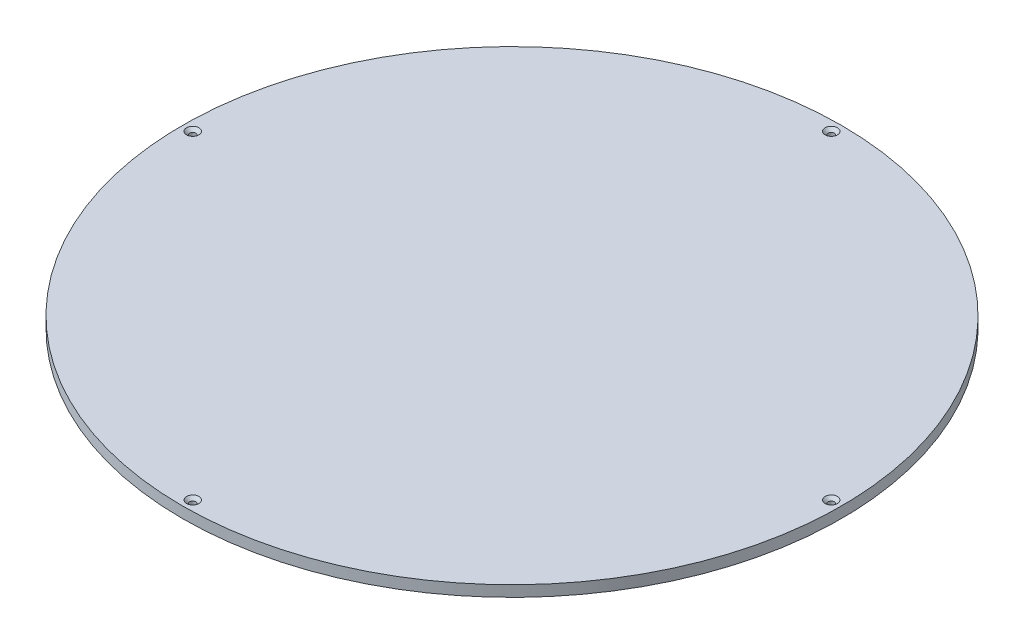
SolidWorks part; units mm, degrees
material "Pine"
ref_plane "Front Plane" through (0, 0, 0) normal (0, 0, 1) x (1, 0, 0)
ref_plane "Top Plane" through (0, 0, 0) normal (0, 1, 0) x (1, 0, 0)
ref_plane "Right Plane" through (0, 0, 0) normal (1, 0, 0) x (0, 0, -1)
sketch "Sketch1" plane through (0, 0, 0) normal (0, 1, 0) x (1, 0, 0)
  line L0 (-8.7941, 0) -> (197.1788, 0) construction
  circle A0 centre (0, 0) radius 160
  circle A1 centre (155, 0) radius 1.5
  circle A2 centre (0, -155) radius 1.5
  circle A3 centre (-155, 0) radius 1.5
  circle A4 centre (0, 155) radius 1.5
  point P16 (0, 0)
  dimension "D1" = 320
  dimension "D2" = 3
  dimension "D3" = 155
  dimension "D4" = 4
extrude "Boss-Extrude1" add sketch "Sketch1" against normal blind 5.333
chamfer "Chamfer1" distance 1.5 angle 45 4 edges at (155, 0, 1.5) (-155, 0, 1.5) (0, 0, -153.5) (0, 0, 156.5)
equation "\"rod_diameter\"= 8"
equation "\"rod_hole_thickness\"= 4"
equation "\"rod_radius\"= \"rod_diameter\" / 2"
equation "\"platter_diameter\"= 320"
equation "\"platter_radius\"= \"platter_diameter\" / 2"
equation "\"extruder_mount_hole_spacing\"= 75"
equation "\"arm_rod_spacing\"= 40"
equation "\"motor_level_rod_spacing\"= 15"
equation "\"linear_bearing_diameter\"= 15"
equation "\"z_rod_spacing\"= 75"
equation "\"platter_rod_spacing\"= 50"
equation "\"rod_nut_thickness\"= 6.5"
equation "\"rod_nut_inscribed_diameter\"= 13"
equation "\"z_height\"= 400"
equation "\"D1@Sketch1\"=\"platter_diameter\""
equation "\"D3@Sketch1\"=\"platter_radius\"-5"
equation "\"top_frame_spacing\"= 100"
equation "\"z_drive_rod_offset\"= 12"
equation "\"gear_pitch\"=2"
equation "\"r_gear_teeth\"= 450"
equation "\"theta_gear_teeth\"= 385"
equation "\"sheet_thickness\"=5.333"
equation "\"sheet_tab_hole_thickness\"= \"sheet_thickness\""
equation "\"sheet_tab_width\"= \"sheet_thickness\"*2"
equation "\"sheet_double_tab_width\"= 35"
equation "\"sheet_bolt_diameter\"= 3"
equation "\"sheet_bolt_length\"= 16"
equation "\"sheet_nut_diameter\"= 5.5"
equation "\"sheet_nut_thickness\"= 2.5"
equation "\"sheet_nut_depth\"= 10"
equation "\"bearing_outside_diameter\"= 22"
equation "\"bearing_thickness\"= 7"
equation "\"corner_part_thickness\"= \"sheet_thickness\" + \"bearing_thickness\""
equation "\"setscrew_nut_diameter\"= 6"
equation "\"setscrew_nut_thickness\"= 3"
equation "\"setscrew_bolt_diameter\"= 3"
equation "\"motor_shaft_diameter\"= 5.7"
equation "\"D1@Boss-Extrude1\"= \"sheet_thickness\""
